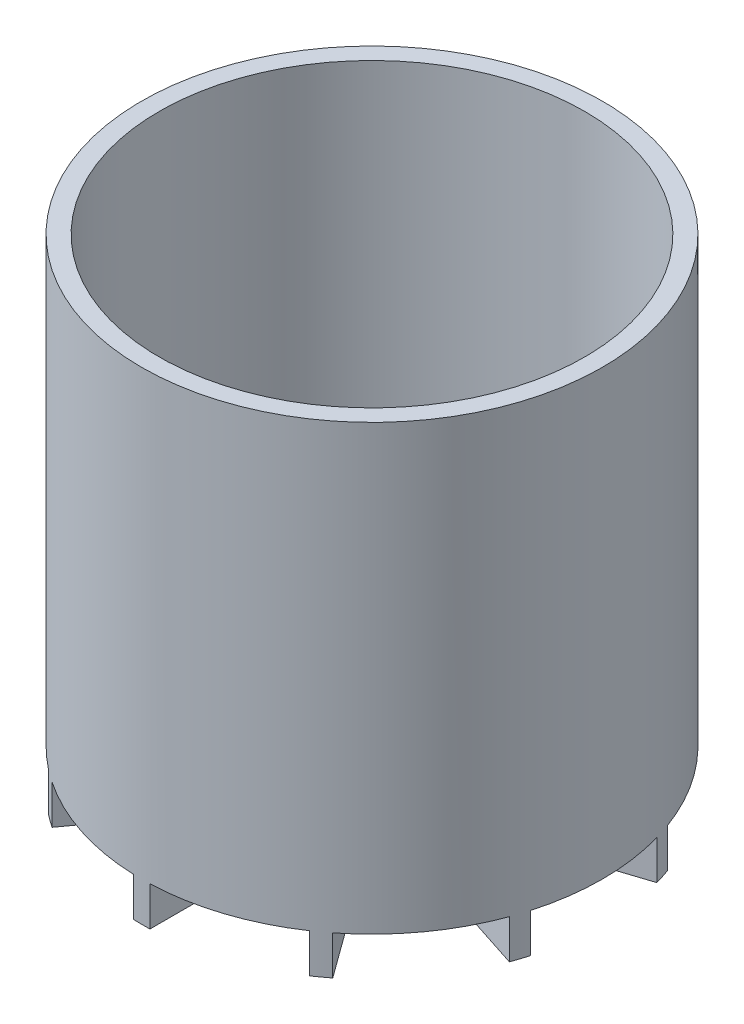
SolidWorks part; units mm, degrees
ref_plane "Front Plane" through (0, 0, 0) normal (0, 0, 1) x (1, 0, 0)
ref_plane "Top Plane" through (0, 0, 0) normal (0, 1, 0) x (1, 0, 0)
ref_plane "Right Plane" through (0, 0, 0) normal (1, 0, 0) x (0, 0, -1)
sketch "Sketch1" plane through (0, 0, 0) normal (0, 1, 0) x (1, 0, 0)
  circle A0 centre (0, 0) radius 38.1
  dimension "D1" = 76.2
extrude "Boss-Extrude1" add sketch "Sketch1" along normal blind 76.2
shell "Shell2" thickness 3.175 removed face at (0, 76.2, 38.1) outward yes
ref_axis "Axis1" through (0, 76.2, 0) along (0, -1, 0)
sketch "Sketch2" plane through (0, -3.175, 0) normal (0, -1, 0) x (-1, 0, 0)
  line L0 (0, 0) -> (0, 41.275)
  line L1 (-1.5, -41.275) -> (-1.5, 41.275)
  line L2 (-1.5, -41.275) -> (1.5, -41.275)
  line L3 (-1.5, 41.275) -> (1.5, 41.275)
  line L4 (1.5, -41.275) -> (1.5, 41.275)
  line L5 (-1.5, -41.275) -> (1.5, 41.275) construction
  line L6 (-1.5, 41.275) -> (1.5, -41.275) construction
  line L7 (-23.0473, -34.2739) -> (25.4744, 32.5105)
  line L8 (-25.4744, -32.5105) -> (23.0473, 34.2739)
  line L9 (-25.4744, -32.5105) -> (-23.0473, -34.2739)
  line L10 (23.0473, 34.2739) -> (25.4744, 32.5105)
  line L11 (-38.7913, -14.1813) -> (39.7184, 11.3281)
  line L12 (-39.7184, -11.3281) -> (38.7913, 14.1813)
  line L13 (-39.7184, -11.3281) -> (-38.7913, -14.1813)
  line L14 (38.7913, 14.1813) -> (39.7184, 11.3281)
  line L15 (-39.7184, 11.3281) -> (38.7913, -14.1813)
  line L16 (-38.7913, 14.1813) -> (39.7184, -11.3281)
  line L17 (-38.7913, 14.1813) -> (-39.7184, 11.3281)
  line L18 (39.7184, -11.3281) -> (38.7913, -14.1813)
  line L19 (-25.4744, 32.5105) -> (23.0473, -34.2739)
  line L20 (-23.0473, 34.2739) -> (25.4744, -32.5105)
  line L21 (-23.0473, 34.2739) -> (-25.4744, 32.5105)
  line L22 (25.4744, -32.5105) -> (23.0473, -34.2739)
  line L23 (-1.5, 41.275) -> (-1.5, -41.275)
  line L24 (1.5, 41.275) -> (1.5, -41.275)
  line L25 (1.5, 41.275) -> (-1.5, 41.275)
  line L26 (1.5, -41.275) -> (-1.5, -41.275)
  line L47 (38.7913, 14.1813) -> (-39.7184, -11.3281)
  line L48 (-38.7913, -14.1813) -> (-39.7184, -11.3281)
  line L49 (39.7184, 11.3281) -> (-38.7913, -14.1813)
  line L50 (39.7184, 11.3281) -> (38.7913, 14.1813)
  line L51 (39.7184, -11.3281) -> (-38.7913, 14.1813)
  line L52 (-39.7184, 11.3281) -> (-38.7913, 14.1813)
  line L53 (38.7913, -14.1813) -> (-39.7184, 11.3281)
  line L54 (38.7913, -14.1813) -> (39.7184, -11.3281)
  line L55 (25.4744, -32.5105) -> (-23.0473, 34.2739)
  line L56 (-25.4744, 32.5105) -> (-23.0473, 34.2739)
  line L57 (23.0473, -34.2739) -> (-25.4744, 32.5105)
  line L58 (23.0473, -34.2739) -> (25.4744, -32.5105)
  line L59 (1.5, 41.275) -> (1.5, -41.275)
  line L60 (1.5, 41.275) -> (-1.5, 41.275)
  line L61 (-1.5, 41.275) -> (-1.5, -41.275)
  line L62 (1.5, -41.275) -> (-1.5, -41.275)
  line L63 (23.0473, 34.2739) -> (-25.4744, -32.5105)
  line L64 (-23.0473, -34.2739) -> (-25.4744, -32.5105)
  line L65 (25.4744, 32.5105) -> (-23.0473, -34.2739)
  line L66 (25.4744, 32.5105) -> (23.0473, 34.2739)
  line L87 (-14.1813, 38.7913) -> (11.3281, -39.7184) [skipped]
  line L88 (14.1813, -38.7913) -> (11.3281, -39.7184) [skipped]
  line L89 (-11.3281, 39.7184) -> (14.1813, -38.7913) [skipped]
  line L90 (-11.3281, 39.7184) -> (-14.1813, 38.7913) [skipped]
  line L91 (-34.2739, 23.0473) -> (32.5105, -25.4744) [skipped]
  line L92 (34.2739, -23.0473) -> (32.5105, -25.4744) [skipped]
  line L93 (-32.5105, 25.4744) -> (34.2739, -23.0473) [skipped]
  line L94 (-32.5105, 25.4744) -> (-34.2739, 23.0473) [skipped]
  line L95 (-41.275, 1.5) -> (41.275, 1.5) [skipped]
  line L96 (41.275, 1.5) -> (41.275, -1.5) [skipped]
  line L97 (-41.275, -1.5) -> (41.275, -1.5) [skipped]
  line L98 (-41.275, 1.5) -> (-41.275, -1.5) [skipped]
  line L99 (32.5105, 25.4744) -> (-34.2739, -23.0473) [skipped]
  line L100 (-32.5105, -25.4744) -> (-34.2739, -23.0473) [skipped]
  line L101 (34.2739, 23.0473) -> (-32.5105, -25.4744) [skipped]
  line L102 (34.2739, 23.0473) -> (32.5105, 25.4744) [skipped]
  line L103 (11.3281, 39.7184) -> (-14.1813, -38.7913) [skipped]
  line L104 (-11.3281, -39.7184) -> (-14.1813, -38.7913) [skipped]
  line L105 (14.1813, 38.7913) -> (-11.3281, -39.7184) [skipped]
  line L106 (14.1813, 38.7913) -> (11.3281, 39.7184) [skipped]
  line L107 (34.2739, -23.0473) -> (-32.5105, 25.4744) [skipped]
  line L108 (-34.2739, 23.0473) -> (-32.5105, 25.4744) [skipped]
  line L109 (32.5105, -25.4744) -> (-34.2739, 23.0473) [skipped]
  line L110 (32.5105, -25.4744) -> (34.2739, -23.0473) [skipped]
  line L111 (14.1813, -38.7913) -> (-11.3281, 39.7184) [skipped]
  line L112 (-14.1813, 38.7913) -> (-11.3281, 39.7184) [skipped]
  line L113 (11.3281, -39.7184) -> (-14.1813, 38.7913) [skipped]
  line L114 (11.3281, -39.7184) -> (14.1813, -38.7913) [skipped]
  line L115 (41.275, -1.5) -> (-41.275, -1.5) [skipped]
  line L116 (-41.275, -1.5) -> (-41.275, 1.5) [skipped]
  line L117 (41.275, 1.5) -> (-41.275, 1.5) [skipped]
  line L118 (41.275, -1.5) -> (41.275, 1.5) [skipped]
  line L119 (-32.5105, -25.4744) -> (34.2739, 23.0473) [skipped]
  line L120 (32.5105, 25.4744) -> (34.2739, 23.0473) [skipped]
  line L121 (-34.2739, -23.0473) -> (32.5105, 25.4744) [skipped]
  line L122 (-34.2739, -23.0473) -> (-32.5105, -25.4744) [skipped]
  line L123 (-11.3281, -39.7184) -> (14.1813, 38.7913) [skipped]
  line L124 (11.3281, 39.7184) -> (14.1813, 38.7913) [skipped]
  line L125 (-14.1813, -38.7913) -> (11.3281, 39.7184) [skipped]
  line L126 (-14.1813, -38.7913) -> (-11.3281, -39.7184) [skipped]
  circle A1 centre (0, 0) radius 41.275 construction
  circle A2 centre (0, 0) radius 41.275
  dimension "D1" = 3
  dimension "D2" = 6
  dimension "D3" = 4
extrude "Boss-Extrude2" add sketch "Sketch2" along normal blind 7 contours L4 L3 L1 L2 | L7 L10 L8 L9 | L11 L14 L12 L13 | L15 L18 L16 L17 | L20 L22 L19 L21
sketch "Sketch3" plane through (0, -3.175, 0) normal (0, -1, 0) x (1, 0, 0)
  circle A0 centre (0, 0) radius 41.275
  circle A1 centre (0, 0) radius 61.9063
extrude "Cut-Extrude1" cut sketch "Sketch3" against normal through all both and the other way through all
sketch "Sketch4" plane through (0, -10.175, 0) normal (0, -1, 0) x (1, 0, 0)
  circle A0 centre (0, 0) radius 20.64
extrude "Cut-Extrude2" cut sketch "Sketch4" against normal up to surface (7 mm away) up to face at (-23.1437, -3.175, 16.8149)
scale "Scale1" scale about centroid uniform scaling yes scale factor 0.615385
